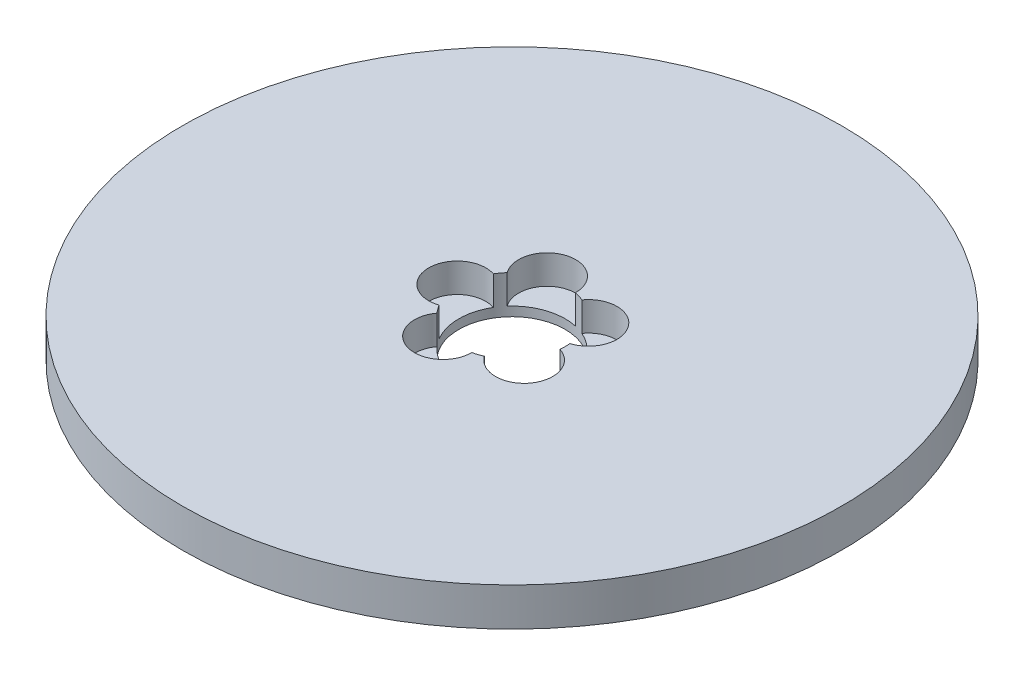
SolidWorks part; units mm, degrees
ref_plane "Front Plane" through (0, 0, 0) normal (0, 0, 1) x (1, 0, 0)
ref_plane "Top Plane" through (0, 0, 0) normal (0, 1, 0) x (1, 0, 0)
ref_plane "Right Plane" through (0, 0, 0) normal (1, 0, 0) x (0, 0, -1)
sketch "Sketch1" plane through (0, 0, 0) normal (0, 1, 0) x (1, 0, 0)
  circle A0 centre (0, 0) radius 77.5
  dimension "FLANGE_OD" = 155
extrude "Boss-Extrude1" add sketch "Sketch1" along normal blind 9
sketch "Sketch2" plane through (0, 0, 0) normal (0, 1, 0) x (1, 0, 0)
  circle A0 centre (0, 0) radius 12.5
  dimension "BORE_D" = 25
extrude "Cut-Extrude1" cut sketch "Sketch2" along normal through all
sketch "Sketch3" plane through (0, 9, 0) normal (0, 1, 0) x (1, 0, 0)
  circle A0 centre (0, 0) radius 12.8728 construction
  circle A1 centre (-12.8728, 0) radius 6.7159
  dimension "BOLT_D" = 13.4317
  dimension "BOLT_PCD" = 25.7456
extrude "Cut-Extrude2" cut sketch "Sketch3" against normal blind 6.8284
pattern_circular "CirPattern1" count 5 over 360 about axis through (0, 0, 0) along (0, 1, 0) of "Cut-Extrude2"
